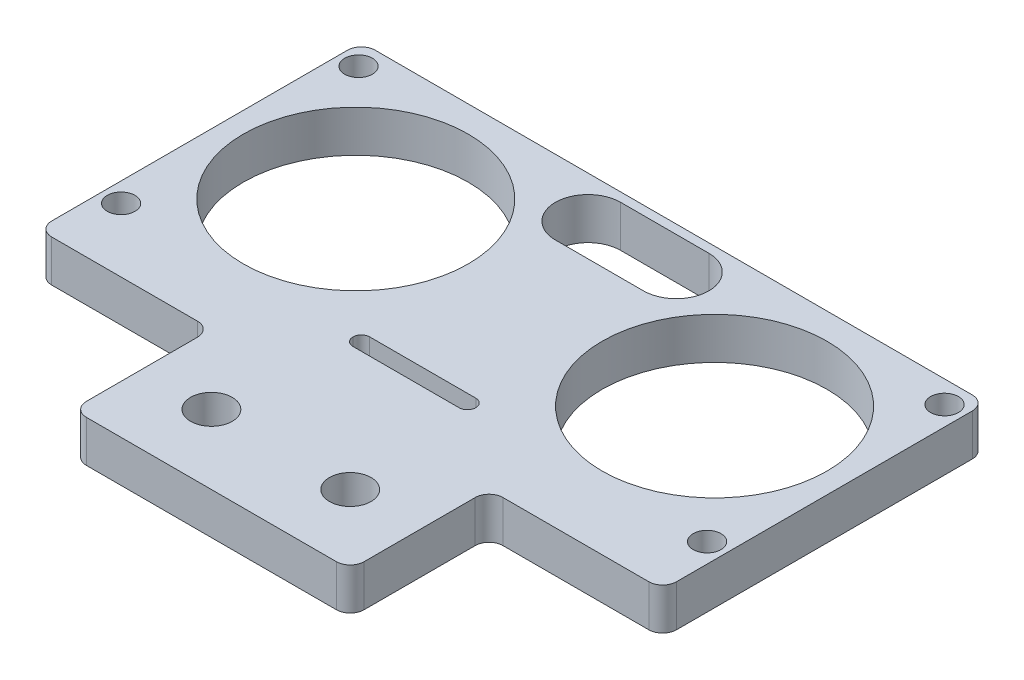
SolidWorks part; units mm, degrees
ref_plane "Front Plane" through (0, 0, 0) normal (0, 0, 1) x (1, 0, 0)
ref_plane "Top Plane" through (0, 0, 0) normal (0, 1, 0) x (1, 0, 0)
ref_plane "Right Plane" through (0, 0, 0) normal (1, 0, 0) x (0, 0, -1)
sketch "Sketch1" plane through (0, 0, 0) normal (0, 1, 0) x (1, 0, 0)
  line L0 (22.5, 20.3) -> (22.5, 0) construction
  line L1 (0, 0) -> (45, 0) construction
  line L2 (0, 0) -> (0, 20.3)
  line L3 (0, 20.3) -> (45, 20.3)
  line L4 (45, 0) -> (45, 20.3)
  line L5 (0, 10.15) -> (45, 10.15) construction
  line L6 (12.5, -3) -> (0, -3)
  line L7 (25.675, 19.65) -> (19.325, 19.65)
  line L9 (25.675, 14.95) -> (19.325, 14.95)
  line L11 (0, 0) -> (45, 0) construction
  line L12 (0, 0) -> (0, -3)
  line L13 (0, -3) -> (45, -3) construction
  line L14 (45, 0) -> (45, -3)
  line L15 (12.5, -3) -> (32.5, -3) construction
  line L16 (12.5, -3) -> (12.5, -13)
  line L17 (12.5, -13) -> (32.5, -13)
  line L18 (32.5, -3) -> (32.5, -13)
  line L19 (32.5, -3) -> (45, -3)
  circle A0 centre (1.4, 18.7) radius 1
  circle A1 centre (1.4, 1.6) radius 1
  circle A2 centre (43.6, 1.6) radius 1
  circle A3 centre (43.6, 18.7) radius 1
  circle A4 centre (9.58, 10.32) radius 8.1
  circle A5 centre (35.42, 10.32) radius 8.1
  arc A6 (19.325, 19.65) -> (19.325, 14.95) centre (19.325, 17.3) ccw
  arc A7 (25.675, 19.65) -> (25.675, 14.95) centre (25.675, 17.3) cw
  circle A8 centre (17.5, -8) radius 1.5
  circle A9 centre (27.5, -8) radius 1.5
  point P33 (22.5, -3)
  point P34 (22.5, -3)
  point P39 (12.5, -8)
  dimension "D3" = 2
  dimension "D4" = 1.6
  dimension "D6" = 16.2
  dimension "D7" = 16.2
  dimension "D16" = 3
  dimension "D17" = 3
  dimension "D1" = 45
  dimension "D2" = 20.3
  dimension "D5" = 1.4
  dimension "D8" = 9.98
  dimension "D9" = 9.58
  dimension "D10" = 9.58
  dimension "D11" = 3
  dimension "D12" = 4.7
  dimension "D13" = 0.65
  dimension "D14" = 10
  dimension "D15" = 20
  dimension "D18" = 5
  dimension "D19" = 5
extrude "Boss-Extrude1" add sketch "Sketch1" along normal blind 3
sketch "Sketch2" plane through (0, 3, 0) normal (0, 1, 0) x (1, 0, 0)
  line L8 (12.5, -13) -> (32.5, -13) construction
  line L9 (18.08, 2.22) -> (26.92, 2.22)
  line L10 (18.08, 2.22) -> (18.08, 1.02)
  line L11 (18.08, 1.02) -> (26.92, 1.02)
  line L12 (26.92, 2.22) -> (26.92, 1.02)
  line L13 (0, 20.3) -> (0, -3) construction
  dimension "D1" = 8.84
  dimension "D2" = 1.2
  dimension "D3" = 14.02
  dimension "D4" = 18.08
extrude "Cut-Extrude1" cut sketch "Sketch2" against normal blind 3
fillet "Fillet1" radius 1 8 edges at (45, 1.5, -20.3) (0, 1.5, -20.3) (0, 1.5, 3) (12.5, 1.5, 3) (12.5, 1.5, 13) (32.5, 1.5, 13) (45, 1.5, 3) (32.5, 1.5, 3)
fillet "Fillet4" radius 0.6 4 edges at (26.92, 1.5, -2.22) (26.92, 1.5, -1.02) (18.08, 1.5, -1.02) (18.08, 1.5, -2.22)
